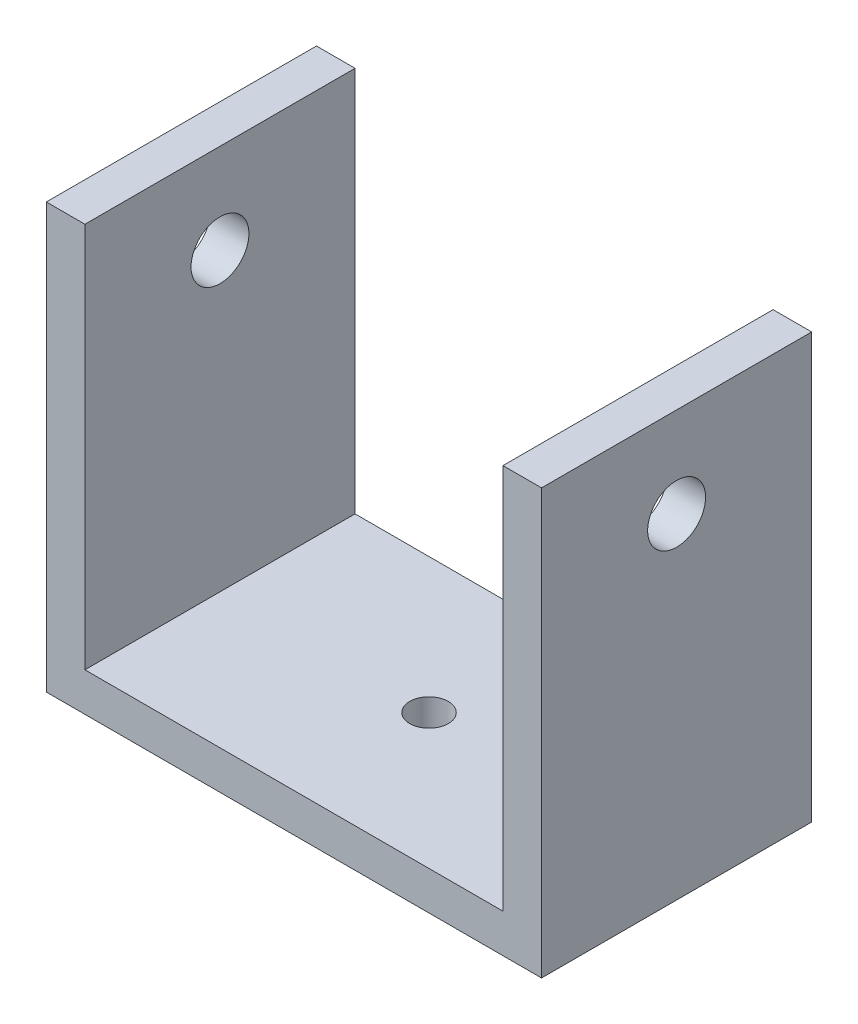
SolidWorks part; units mm, degrees
ref_plane "Front Plane" through (0, 0, 0) normal (0, 0, 1) x (1, 0, 0)
ref_plane "Top Plane" through (0, 0, 0) normal (0, 1, 0) x (1, 0, 0)
ref_plane "Right Plane" through (0, 0, 0) normal (1, 0, 0) x (0, 0, -1)
sketch "Sketch1" plane through (0, 0, 0) normal (0, 1, 0) x (1, 0, 0)
  line L1 (-16.25, -10.5) -> (16.25, -10.5)
  line L2 (-16.25, -10.5) -> (-16.25, 10.5)
  line L3 (-16.25, 10.5) -> (16.25, 10.5)
  line L4 (16.25, -10.5) -> (16.25, 10.5)
  line L5 (-16.25, -10.5) -> (16.25, 10.5) construction
  line L6 (-16.25, 10.5) -> (16.25, -10.5) construction
  line L7 (-16.25, 10.5) -> (-19.25, 10.5)
  line L8 (-16.25, 10.5) -> (-16.25, -10.5)
  line L9 (-16.25, -10.5) -> (-19.25, -10.5)
  line L10 (-19.25, 10.5) -> (-19.25, -10.5)
  line L11 (16.25, 10.5) -> (19.25, 10.5)
  line L12 (16.25, 10.5) -> (16.25, -10.5)
  line L13 (16.25, -10.5) -> (19.25, -10.5)
  line L14 (19.25, 10.5) -> (19.25, -10.5)
  point P0 (0, 0)
  dimension "D1" = 32.5
  dimension "D2" = 21
  dimension "D3" = 3
  dimension "D4" = 3
extrude "Boss-Extrude1" add sketch "Sketch1" along normal blind 3 contours L1 L4 L3 L2 region at (0, 0, 0)
extrude "Boss-Extrude2" add sketch "Sketch1<3>" along normal blind 33 contours L7 L10 L9 L2 | L14 L11 L4 L13 region at (-17.75, 0, 0) region at (17.75, 0, 0)
sketch "Sketch1<3>" plane through (0, 0, 0) normal (0, 1, 0) x (1, 0, 0) same geometry as "Sketch1"
sketch "Sketch2" plane through (19.25, 0, 0) normal (1, 0, 0) x (0, 0, -1)
  line L0 (10.5, 33) -> (-10.5, 33) construction
  circle A0 centre (0, 26) radius 2.25
  dimension "D2" = 4.5
  dimension "D1" = 7
extrude "Cut-Extrude1" cut sketch "Sketch2" against normal through all
sketch "Sketch3" plane through (0, 3, 0) normal (0, 1, 0) x (1, 0, 0)
  circle A0 centre (0, 0) radius 1.5
  dimension "D1" = 3
extrude "Cut-Extrude2" cut sketch "Sketch3" against normal through all
